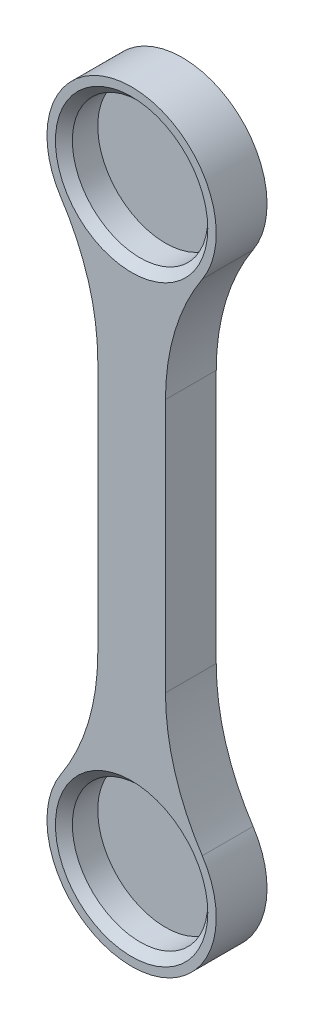
SolidWorks part; units mm, degrees
ref_plane "Plan de face" through (0, 0, 0) normal (0, 0, 1) x (1, 0, 0)
ref_plane "Plan de dessus" through (0, 0, 0) normal (0, 1, 0) x (1, 0, 0)
ref_plane "Plan de droite" through (0, 0, 0) normal (1, 0, 0) x (0, 0, -1)
sketch "Esquisse1" plane through (0, 0, 0) normal (0, 0, 1) x (1, 0, 0)
  line L0 (-10, 0) -> (-10, 70)
  line L1 (10, 0) -> (10, 70)
  arc A0 (-10, 0) -> (10, 0) centre (0, 0) ccw
  arc A1 (10, 70) -> (-10, 70) centre (0, 70) ccw
  dimension "D1" = 70
  dimension "D2" = 10
extrude "Boss.-Extru.1" add sketch "Esquisse1" along normal blind 6
sketch "Esquisse2" plane through (0, 0, 6) normal (0, 0, 1) x (1, 0, 0)
  circle A0 centre (0, 0) radius 8
  circle A1 centre (0, 70) radius 8
  arc A2 (10, 70) -> (-10, 70) centre (0, 70) ccw construction
  dimension "D1" = 16
extrude "Enlèv. mat.-Extru.1" cut sketch "Esquisse2" against normal blind 4
sketch "Esquisse3" plane through (0, 0, 6) normal (0, 0, 1) x (1, 0, 0)
  line L0 (-4, 50) -> (-4, 20)
  line L1 (-10, 35) -> (10, 35) construction
  line L2 (-10, 70) -> (-10, 0) construction
  line L3 (10, 0) -> (10, 70) construction
  line L4 (0, -4.4) -> (0, 4.4) construction
  line L5 (4, 50) -> (4, 20)
  line L6 (-10, 70) -> (-10, 0)
  line L7 (10, 0) -> (10, 70)
  arc A0 (10, 0) -> (8.3486, 5.5046) centre (0, 0) ccw
  arc A2 (-8.3486, 5.5046) -> (-4, 20) centre (-30.3333, 20) ccw
  arc A3 (8.3486, 64.4954) -> (10, 70) centre (0, 70) ccw
  arc A4 (10, 70) -> (-10, 70) centre (0, 70) ccw construction
  arc A6 (-8.3486, 64.4954) -> (-4, 50) centre (-30.3333, 50) cw
  arc A7 (8.3486, 5.5046) -> (4, 20) centre (30.3333, 20) cw
  arc A8 (8.3486, 64.4954) -> (4, 50) centre (30.3333, 50) ccw
  arc A9 (-8.3486, 5.5046) -> (-10, 0) centre (0, 0) ccw
  arc A10 (-10, 70) -> (-8.3486, 64.4954) centre (0, 70) ccw
  point P23 (0, 35)
  point P28 (-4, 35)
  dimension "D1" = 4
  dimension "D2" = 15
extrude "Enlèv. mat.-Extru.2" cut sketch "Esquisse3" against normal through all
chamfer "Chanfrein1" distance 1 angle 45 2 edges at (8, 0, 6) (8, 70, 6)
